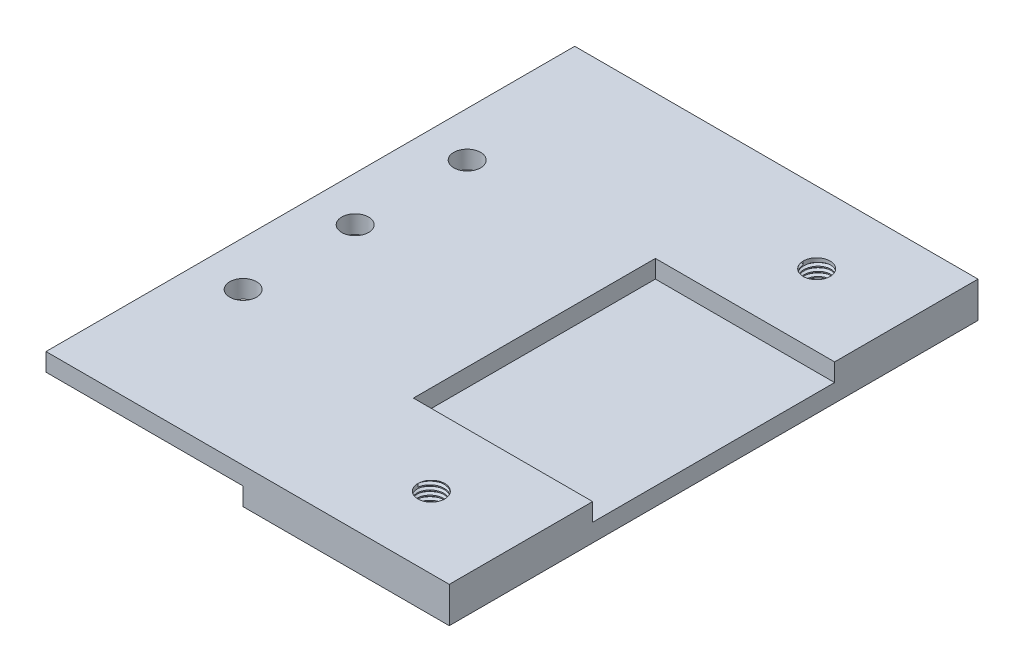
SolidWorks part; units mm, degrees
material "ABS"
ref_plane "前视基准面" through (0, 0, 0) normal (0, 0, 1) x (1, 0, 0)
ref_plane "上视基准面" through (0, 0, 0) normal (0, 1, 0) x (1, 0, 0)
ref_plane "右视基准面" through (0, 0, 0) normal (1, 0, 0) x (0, 0, -1)
sketch "草图1" plane through (0, 0, 0) normal (0, 0, 1) x (1, 0, 0)
  line L8 (0, 0) -> (23, 0)
  line L9 (23, 0) -> (23, 2)
  line L10 (23, 2) -> (3, 2)
  line L11 (3, 2) -> (3, 4)
  line L12 (3, 4) -> (-22, 4)
  line L13 (-22, 4) -> (-22, 2)
  line L14 (-22, 2) -> (0, 2)
  line L15 (0, 2) -> (0, 0)
  dimension "D1" = 2
  dimension "D2" = 2
  dimension "D3" = 20
  dimension "D4" = 25
  dimension "D5" = 4
  dimension "D6" = 3
extrude "载玻片底座" add sketch "草图1" along normal blind 29.5 and the other way blind 29.5
sketch "草图2" plane through (0, 4, 0) normal (0, 1, 0) x (1, 0, 0)
  line L0 (-17, 29.5) -> (-17, -28.7651) construction
  line L2 (0, -29.5) -> (0, 29.5) construction
  line L5 (0, 0) -> (-30, 0) construction
  circle A0 centre (-17, -12.5) radius 1.5
  circle A1 centre (-17, 0) radius 1.5
  circle A2 centre (-17, 12.5) radius 1.5
  dimension "D1" = 3
  dimension "D2" = 17
  dimension "D3" = 12.5
  dimension "D4" = 12.5
extrude "M3*3 定位孔" cut sketch "草图2" against normal through all
sketch "草图3" plane through (0, 2, 0) normal (0, 1, 0) x (1, 0, 0)
  line L1 (23, -29.5) -> (3, -29.5)
  line L2 (23, -29.5) -> (23, -13.5)
  line L3 (23, -13.5) -> (3, -13.5)
  line L4 (3, 29.5) -> (3, -29.5)
  line L5 (3, -29.5) -> (23, -29.5)
  line L6 (23, -29.5) -> (23, 29.5)
  line L7 (23, 29.5) -> (3, 29.5)
  line L8 (3, 29.5) -> (3, -29.5)
  line L9 (3, -29.5) -> (23, -29.5)
  line L10 (23, -29.5) -> (23, 29.5)
  line L11 (23, 29.5) -> (3, 29.5)
  line L12 (3, -29.5) -> (3, -13.5)
  line L13 (23, 29.5) -> (3, 29.5)
  line L14 (23, 29.5) -> (23, 13.5)
  line L15 (23, 13.5) -> (3, 13.5)
  line L16 (3, 29.5) -> (3, 13.5)
  line M8 (3, 29.5) -> (3, -29.5)
  line M9 (3, -29.5) -> (23, -29.5)
  line M10 (23, -29.5) -> (23, 29.5)
  line M11 (23, 29.5) -> (3, 29.5)
  dimension "D2" = 16
  dimension "D3" = 16
  dimension "D4" = 27
  dimension "D1" = 0
extrude "载玻片定位" add sketch "草图3" along normal blind 2 contours L3 M10 M8 M9 | L15 L10 M11 M8 region at (13, 2, 21.5) region at (13, 2, -21.5)
sketch "草图4" plane through (0, 4, 0) normal (0, 1, 0) x (1, 0, 0)
  line L6 (-22, -29.5) -> (23, -29.5) construction
  line L8 (23, -29.5) -> (23, -13.5) construction
  circle A0 centre (13, -21.5) radius 1.5
  dimension "D1" = 3
  dimension "D2" = 8
  dimension "D3" = 10
extrude "M3*2 固定孔" cut sketch "草图4" against normal through all
thread "M3*2 固定孔螺纹线" pitch 0.5 method cut profile "螺纹线轮廓1" start angle 0, offset 0, length 5, pitch 0.5, diameter 3
ref_plane "基准面1" through (11.5, 4, 21.5) normal (0, 0, 1) x (-1, 0, 0)
sketch "螺纹线轮廓1" plane through (11.5, 4, 21.5) normal (0, 0, 1) x (-1, 0, 0)
  line L0 (0, 0) -> (0, 0.5) construction
  line L1 (0, 0) -> (0.2706, 0.1562)
  line L2 (0.2706, 0.1562) -> (0.2706, 0.2187)
  line L3 (0.2706, 0.2187) -> (0, 0.375)
  line L4 (0.2706, 0.1875) -> (0, 0.1875) construction
  line L11 (0, 0) -> (0, 0.375)
  point P2 (0, 0)
  dimension "Pitch" = 0.5
  dimension "Profile_Angle" = 60
  dimension "Profile_Land" = 0.0625
  dimension "Profile_Height" = 0.2706
mirror "M3*2 固定孔镜像" about plane through (0, 0, 0) normal (0, 0, 1) of "M3*2 固定孔螺纹线", "M3*2 固定孔"
